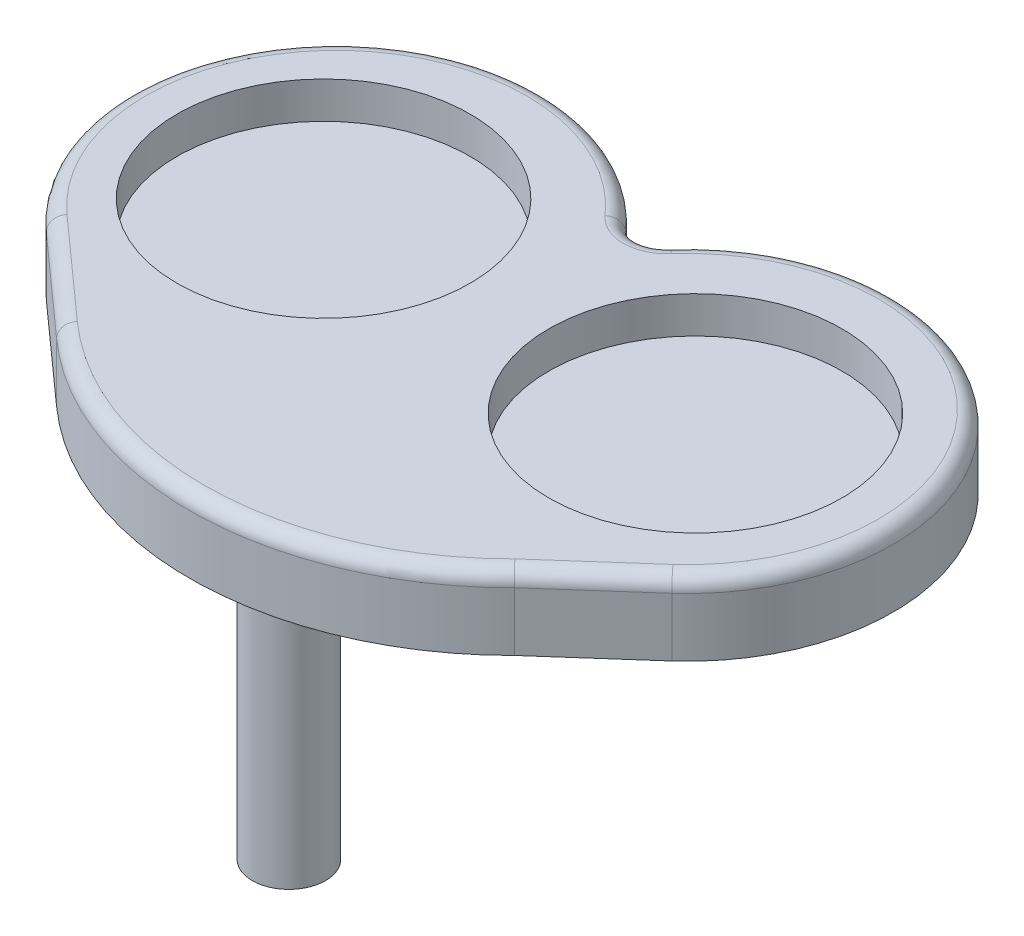
SolidWorks part; units mm, degrees
ref_plane "Front Plane" through (0, 0, 0) normal (0, 0, 1) x (1, 0, 0)
ref_plane "Top Plane" through (0, 0, 0) normal (0, 1, 0) x (1, 0, 0)
ref_plane "Right Plane" through (0, 0, 0) normal (1, 0, 0) x (0, 0, -1)
sketch "Sketch2" plane through (0, 0, 0) normal (0, 1, 0) x (1, 0, 0)
  line L2 (-32.5155, -13.2524) -> (-24.0488, -20.8252)
  line L3 (21.6712, -13.2524) -> (14.4307, -19.6598)
  arc A2 (-5.4222, 9.1581) -> (-32.5155, -13.2524) centre (-20.6622, 0) ccw
  arc A3 (21.6712, -13.2524) -> (-5.4222, 9.1581) centre (9.8178, 0) ccw
  arc A4 (-24.0488, -20.8252) -> (14.4307, -19.6598) centre (-5.4222, 0) ccw
  point P2 (0, 0)
  point P4 (0, 0)
extrude "Boss-Extrude1" add sketch "Sketch2" along normal blind 6.35 contours A2 L2 A4 L3 A3
fillet "Fillet1" radius 2.54 1 edges at (-5.4222, 3.175, -9.1581)
sketch "Sketch3" plane through (0, 6.35, 0) normal (0, 1, 0) x (1, 0, 0)
  circle A0 centre (-21.748, 0) radius 12.7
  circle A1 centre (10.4631, 0) radius 12.7
extrude "Cut-Extrude1" cut sketch "Sketch3" against normal blind 3.175
fillet "Fillet3" radius 1.27 6 edges at (18.0509, 6.35, 16.4561) (22.3462, 6.35, -12.6162) (-5.4222, 6.35, -10.9004) (-33.1905, 6.35, -12.6162) (-28.2822, 6.35, 17.0388) (-4.5763, 6.35, 27.9272)
sketch "Sketch4" plane through (0, 0, 0) normal (0, -1, 0) x (1, 0, 0)
  circle A2 centre (-5.4222, 19.3277) radius 3.175
extrude "Boss-Extrude2" add sketch "Sketch4" along normal blind 25.4 contours A2
fillet "Fillet4" radius 2.54 1 edges at (-5.4222, 0, 22.5027)
